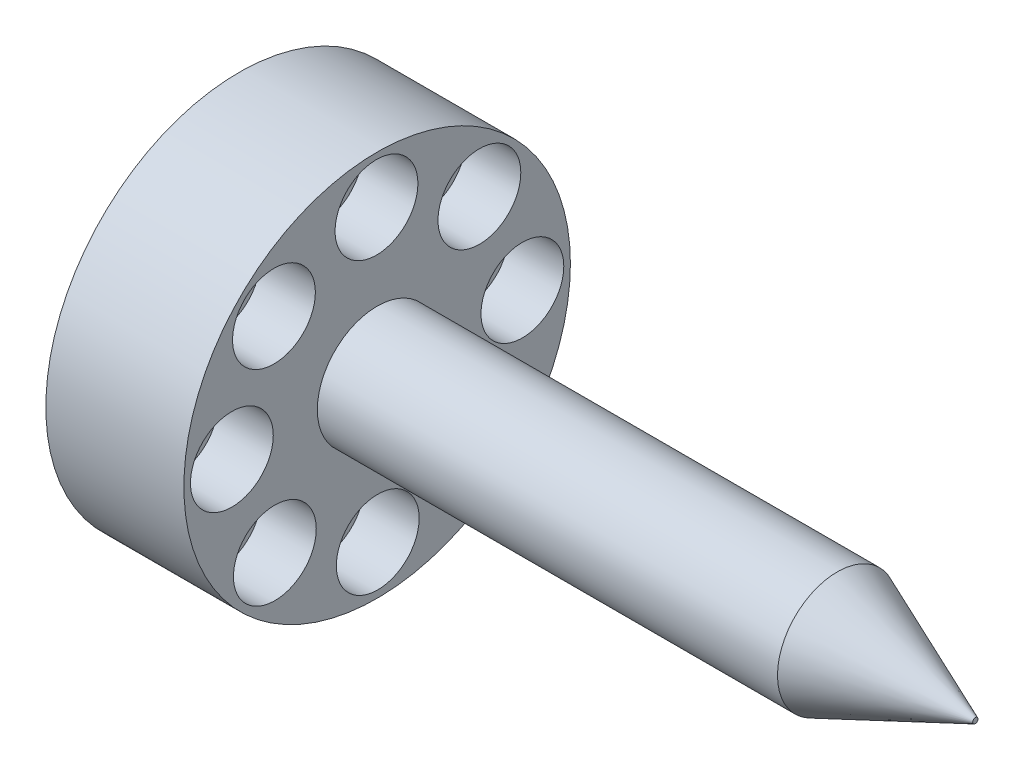
SolidWorks part; units mm, degrees
ref_plane "Plano frontal" through (0, 0, 0) normal (0, 0, 1) x (1, 0, 0)
ref_plane "Plano superior" through (0, 0, 0) normal (0, 1, 0) x (1, 0, 0)
ref_plane "Plano direito" through (0, 0, 0) normal (1, 0, 0) x (0, 0, -1)
sketch "Esboço1" plane through (470, 0, 0) normal (1, 0, 0) x (0, 0, -1)
  circle A0 centre (-750, 0) radius 21
extrude "Ressalto-extrusão1" add sketch "Esboço1" along normal blind 15
sketch "Esboço2" plane through (485, 0, 0) normal (1, 0, 0) x (0, 0, -1)
  circle A0 centre (-750, 0) radius 6.5
  dimension "D1" = 13
extrude "Ressalto-extrusão2" add sketch "Esboço2" along normal blind 65
chamfer "Chanfro1" distance 15 angle 22.5 1 edges at (550, 0, 743.5) first distance on face at (550, 0, 743.5)
sketch "Esboço3" plane through (485, 0, 0) normal (1, 0, 0) x (0, 0, -1)
  circle A0 centre (-738.8848, 11.1587) radius 2.5
  circle A1 centre (-765.7862, -0.0181) radius 4.5
  circle A3 centre (-734.25, 0.0308) radius 2.5
  circle A4 centre (-738.8413, -11.1152) radius 2.5
  circle A5 centre (-749.9692, -15.75) radius 2.5
  circle A6 centre (-761.1152, -11.1587) radius 2.5
  circle A7 centre (-765.75, -0.0308) radius 2.5
  circle A8 centre (-761.1587, 11.1152) radius 2.5
  circle A9 centre (-750.0308, 15.75) radius 2.5
  circle A10 centre (-765.75, -0.0308) radius 3.7499
  circle A11 centre (-761.1152, -11.1587) radius 4.5
  circle A12 centre (-761.2115, 11.1624) radius 4.5
  circle A13 centre (-750.0709, 15.8334) radius 4.5
  circle A14 centre (-738.8904, 11.2587) radius 4.5
  circle A15 centre (-734.2194, 0.1182) radius 4.5
  circle A16 centre (-738.7941, -11.0623) radius 4.5
  circle A17 centre (-749.9347, -15.7333) radius 4.5
  point P23 (-750, 0)
  point P39 (-750.0028, 0.05)
  dimension "D3" = 5
  dimension "D1" = 8
  dimension "D2" = 8
extrude "Corte-extrusão2" cut sketch "Esboço3" against normal blind 4000 contours A8 | A9 | A0 | A3 | A4 | A7 | A6 | A5
extrude "Corte-extrusão3" cut sketch "Esboço3<3>" against normal blind 6 contours A13 A9 | A14 A0 | A15 A3 | A16 A4 | A17 A5 | A11 A6 | A10 A1 | A10 A7 | A12 A8 region at (485, -0.0181, 770.1589) region at (485, -0.0308, 769.3938) region at (485, -11.1587, 765.4879) region at (485, 11.1624, 765.5842) region at (485, 15.8334, 754.4436) region at (485, 11.2587, 743.2631) region at (485, 0.1182, 738.5921) region at (485, -11.0623, 743.1668) region at (485, -15.7333, 754.3074)
sketch "Esboço3<3>" plane through (485, 0, 0) normal (1, 0, 0) x (0, 0, -1) same geometry as "Esboço3"
